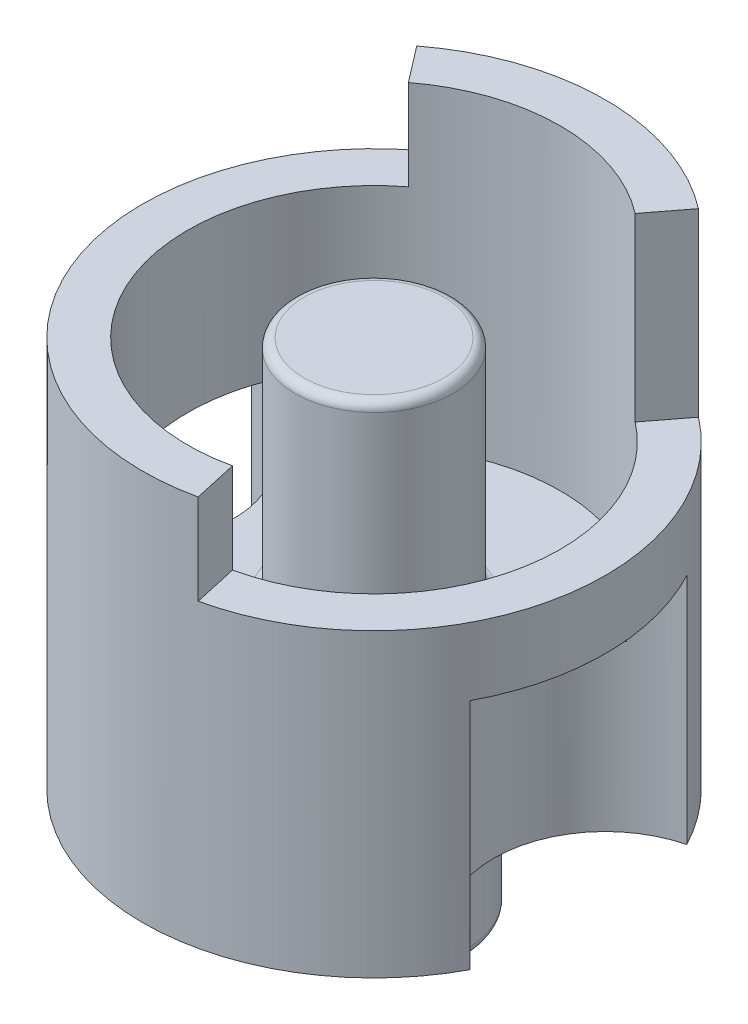
SolidWorks part; units mm, degrees
material "Zinc AC41A Alloy, As Cast"
ref_plane "Front" through (0, 0, 0) normal (0, 0, 1) x (1, 0, 0)
ref_plane "Top" through (0, 0, 0) normal (0, 1, 0) x (1, 0, 0)
ref_plane "Right" through (0, 0, 0) normal (1, 0, 0) x (0, 0, -1)
sketch "Sketch1" plane through (0, 0, 0) normal (0, 1, 0) x (1, 0, 0)
  circle A0 centre (0, 0) radius 6.5087
  dimension "D1" = 13.0175
extrude "Boss-Extrude1" add sketch "Sketch1" along normal blind 13.5382
sketch "Sketch2" plane through (0, 0, 0) normal (0, -1, 0) x (1, 0, 0)
  circle A0 centre (0, 0) radius 2.54
  dimension "D1" = 5.08
extrude "Boss-Extrude2" add sketch "Sketch2" along normal blind 2.921
sketch "Sketch3" plane through (0, 13.5382, 0) normal (0, 1, 0) x (1, 0, 0)
  line L0 (0, 0) -> (-3.9623, 5.1637) construction
  line L1 (0, 0) -> (3.9623, 5.1637) construction
  line L2 (-3.1891, 4.1562) -> (-3.9623, 5.1637)
  line L3 (3.1891, 4.1562) -> (3.9623, 5.1637)
  arc A0 (3.9623, 5.1637) -> (-3.9623, 5.1637) centre (0, 0) ccw construction
  circle A1 centre (0, 0) radius 6.5087 construction
  arc A2 (-3.1891, 4.1562) -> (3.1891, 4.1562) centre (0, 0) cw
  arc A3 (-3.9623, 5.1637) -> (3.9623, 5.1637) centre (0, 0) ccw
  point P10 (0, 6.5087)
  dimension "D2" = 1.27
  dimension "D1" = 75
extrude "Cut-Extrude1" cut sketch "Sketch3" against normal blind 2.54
sketch "Sketch4" plane through (0, 10.9982, 0) normal (0, 1, 0) x (1, 0, 0)
  line L0 (3.9623, 5.1637) -> (3.1891, 4.1562)
  line L1 (1.4088, -6.3545) -> (1.1339, -5.1146)
  line L2 (1.4088, -6.3545) -> (0, 0) construction
  line L3 (3.1891, 4.1562) -> (1.1339, -5.1146) construction
  circle A0 centre (0, 0) radius 2.2225
  arc A1 (3.9623, 5.1637) -> (1.4088, -6.3545) centre (0, 0) cw
  arc A2 (-3.9623, 5.1637) -> (3.9623, 5.1637) centre (0, 0) ccw construction
  arc A3 (3.1891, 4.1562) -> (1.1339, -5.1146) centre (0, 0) ccw
  dimension "D1" = 4.445
  dimension "D2" = 130
extrude "Cut-Extrude2" cut sketch "Sketch4" against normal blind 2.54
sketch "Sketch5" plane through (0, 8.4582, 0) normal (0, 1, 0) x (1, 0, 0)
  circle A0 centre (0, 0) radius 5.2387
  circle A1 centre (0, 0) radius 2.2225
  arc A2 (-3.1891, 4.1562) -> (1.1339, -5.1146) centre (0, 0) ccw construction
  circle A3 centre (0, 0) radius 2.2225 construction
extrude "Cut-Extrude3" cut sketch "Sketch5" against normal blind 3.81
sketch "Sketch6" plane through (0, 0, 0) normal (0, -1, 0) x (1, 0, 0)
  arc A0 (5.751, 3.048) -> (5.751, -3.048) centre (6.5087, 0) ccw
  circle A1 centre (0, 0) radius 6.5087 construction
  arc A2 (-5.9927, 2.54) -> (-5.9927, -2.54) centre (-6.5087, 0) cw
  arc A3 (-5.9927, 2.54) -> (-5.9927, -2.54) centre (0, 0) ccw
  arc A4 (5.751, -3.048) -> (5.751, 3.048) centre (0, 0) ccw
extrude "Cut-Extrude4" cut sketch "Sketch6" against normal offset from surface (6.5532 mm away) 1.905 up to face at (4.079, 8.4582, 0.9043)
fillet "Fillet2" radius 0.254 3 edges at (0, 4.6482, 2.2225) (0, -2.921, -2.54) (0, 10.9982, 2.2225)
